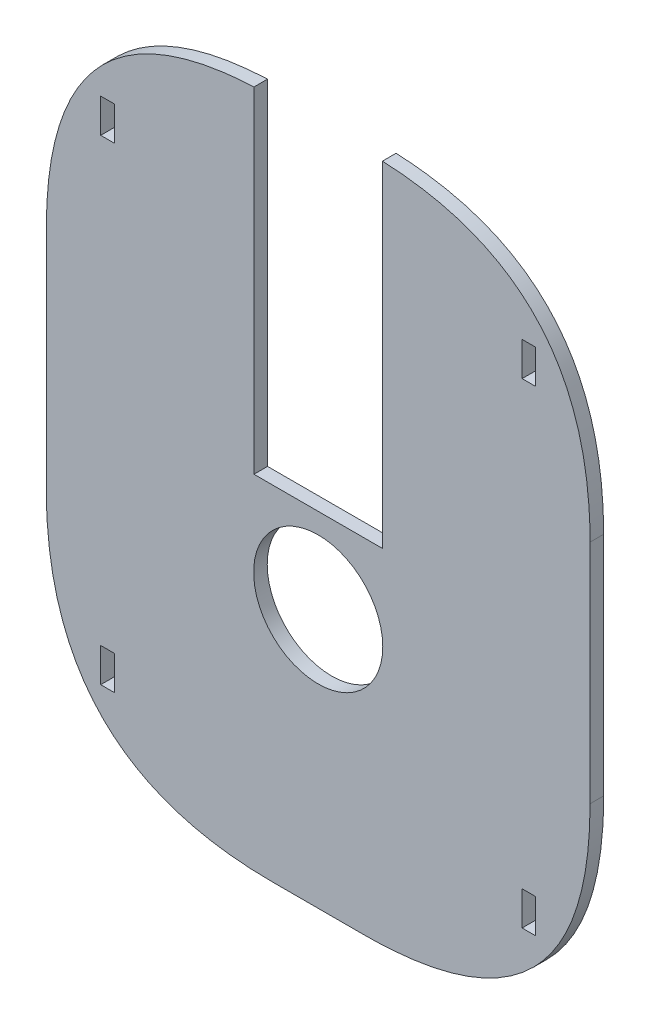
SolidWorks part; units mm, degrees
ref_plane "Front Plane" through (0, 0, 0) normal (0, 0, 1) x (1, 0, 0)
ref_plane "Top Plane" through (0, 0, 0) normal (0, 1, 0) x (1, 0, 0)
ref_plane "Right Plane" through (0, 0, 0) normal (1, 0, 0) x (0, 0, -1)
sketch "Sketch1" plane through (0, 0, 0) normal (0, 0, 1) x (1, 0, 0)
  line L1 (0, 0) -> (203.2, 0)
  line L2 (0, 0) -> (0, 254)
  line L3 (0, 254) -> (203.2, 254)
  line L4 (203.2, 0) -> (203.2, 254)
  dimension "D1" = 254
extrude "Boss-Extrude1" add sketch "Sketch1" along normal blind 5.08
fillet "Fillet1" radius 84.6667 4 edges at (203.2, 254, 2.54) (0, 254, 2.54) (203.2, 0, 2.54) (0, 0, 2.54) conic rho 0.5
sketch "Sketch2" plane through (0, 0, 5.08) normal (0, 0, 1) x (1, 0, 0)
  line L0 (101.6, 254) -> (101.6, 0) construction
  line L1 (118.5333, 254) -> (84.6667, 254) construction
  line L2 (84.6667, 0) -> (118.5333, 0) construction
  line L3 (0, 96.7467) -> (203.2, 96.7467) construction
  line L4 (0, 169.3333) -> (0, 84.6667) construction
  line L5 (203.2, 84.6667) -> (203.2, 169.3333) construction
  circle A0 centre (101.6, 96.7467) radius 24.13
extrude "Cut-Extrude1" cut sketch "Sketch2" against normal through all
sketch "Sketch7" plane through (0, 0, 5.08) normal (0, 0, 1) x (1, 0, 0)
  line L8 (101.6, 215.9) -> (177.8, 215.9) construction
  line L25 (101.6, 38.1) -> (177.8, 38.1) construction
  line L26 (25.4, 215.9) -> (25.4, 222.25)
  line L27 (25.4, 215.9) -> (101.6, 215.9) construction
  line L28 (101.6, 254) -> (101.6, 0) construction
  line L29 (25.4, 222.25) -> (20.32, 222.25)
  line L30 (25.4, 38.1) -> (101.6, 38.1) construction
  line L31 (0, 127) -> (203.2, 127) construction
  line L32 (0, 169.3333) -> (0, 84.6667) construction
  line L33 (203.2, 84.6667) -> (203.2, 169.3333) construction
  line L42 (20.32, 222.25) -> (20.32, 209.55)
  line L43 (20.32, 209.55) -> (25.4, 209.55)
  line L44 (25.4, 209.55) -> (25.4, 215.9)
  line L45 (177.8, 215.9) -> (177.8, 222.25)
  line L46 (177.8, 222.25) -> (182.88, 222.25)
  line L47 (182.88, 222.25) -> (182.88, 209.55)
  line L48 (182.88, 209.55) -> (177.8, 209.55)
  line L49 (177.8, 209.55) -> (177.8, 215.9)
  line L50 (177.8, 38.1) -> (177.8, 44.45)
  line L51 (177.8, 44.45) -> (182.88, 44.45)
  line L52 (182.88, 44.45) -> (182.88, 31.75)
  line L53 (182.88, 31.75) -> (177.8, 31.75)
  line L54 (177.8, 31.75) -> (177.8, 38.1)
  line L55 (25.4, 38.1) -> (25.4, 44.45)
  line L56 (25.4, 44.45) -> (20.32, 44.45)
  line L57 (20.32, 44.45) -> (20.32, 31.75)
  line L58 (20.32, 31.75) -> (25.4, 31.75)
  line L59 (25.4, 31.75) -> (25.4, 38.1)
  dimension "D5" = 88.9
  dimension "D6" = 88.9
  dimension "D3" = 5.08
sketch "Sketch8" plane through (0, 0, 5.08) normal (0, 0, 1) x (1, 0, 0)
  line L0 (-9.9963, 128.4967) -> (213.0772, 128.4967) construction
  line L1 (77.597, 254) -> (125.603, 254)
  line L2 (77.597, 254) -> (77.597, 128.4967)
  line L3 (77.597, 128.4967) -> (125.603, 128.4967)
  line L4 (125.603, 254) -> (125.603, 128.4967)
  line L5 (0, 96.7467) -> (203.2, 96.7467) construction
  line L6 (101.6, 254) -> (101.6, 0) construction
  line L7 (118.5333, 254) -> (84.6667, 254) construction
  point P9 (101.6, 254)
  dimension "D1" = 48.006
  dimension "D2" = 31.75
extrude "Cut-Extrude6" cut sketch "Sketch8" against normal through all
sketch "Sketch9" plane through (0, 0, 0) normal (0, 0, 1) x (1, 0, 0)
  line L1 (60.3112, -121.1497) -> (139.8132, -121.1497) construction
  line L2 (60.3112, -121.1497) -> (60.3112, -43.4257) construction
  line L3 (60.3112, -43.4257) -> (139.8132, -43.4257) construction
  line L4 (139.8132, -121.1497) -> (139.8132, -43.4257) construction
  dimension "D1" = 79.502
  dimension "D2" = 77.724
extrude "Cut-Extrude7" cut sketch "Sketch7" against normal through all
equation "\"FoamCore\" = \".2\""
equation "\"MDF\" = \".2\""
equation "\"GMaterial\"= \".2\""
equation "\"PVCMountDiameter\" = \"0.5in\""
equation "\"PVCMountDistanceToEdge\" = \"0.5\""
equation "\"PVCThickness\" = \"0.13in\""
equation "\"BaseWidth\" = \"8in\""
equation "\"BaseLength\" = \"10in\""
equation "\"BallDiameter\" = \"38mm\""
equation "\"BaseGap\" = \"4in\""
equation "\"FunnelTopDiameter\" = \"8in\""
equation "\"FunnelTopDepth\" = \"0.5in\""
equation "\"BallGap\" = \"0.1in\""
equation "\"FunnelLength\" = 3in"
equation "\"FunnelMaterial\" = 0.1in"
equation "\"FunnelLowerDiameter\" = 1.9in"
equation "\"FunnelDepth\" = 1.5in"
equation "\"AmmoFeederLength\" = 1.5in + 76mm"
equation "\"AmmoFeederCutoffLength\"= \"MovingWheelDiameter\""
equation "\"WheelThickness\" = 0.5in"
equation "\"LauncherWheelDiameter\" = 76mm"
equation "\"MotorFrontLength\" = 0.95in"
equation "\"MotorBodyTotalLength\" = 2.03in"
equation "\"MotorFrontDiameter\" = 1.5in"
equation "\"MotorLowerDriveshaftDiameter\" = 0.46in"
equation "\"MotorLowerDriveshaftThickness\" = 0.25in"
equation "\"MotorFullDriveshaftLength\" = 0.78in"
equation "\"MotorDriveshaftDiameter\" = 0.23in"
equation "\"MotorDriveshaftFlatThickness\" = 0.2in"
equation "\"MotorRearDiameter\" = 31.9mm"
equation "\"MotorDriveshaftBottomToTop\" = 31.1mm"
equation "\"MotorFlatDriveshaftLength\" = 11.7mm"
equation "\"MotorDistanceBetweenLowerandTopHoles\" = 0.5in"
equation "\"MotorMountsDistanceFromEdge\" = 0.06in"
equation "\"MotorScrewMountDiameter\" = 0.1in"
equation "\"MotorScrewMountDepth\" = 0.13in"
equation "\"HBRidgeScrewHoleDeep\" = 0.18in"
equation "\"D1@Sketch1\"=\"BaseLength\""
equation "\"D2@Sketch1\"=\"BaseWidth\""
equation "\"D1@Boss-Extrude1\"=\"MDF\""
equation "\"D1@Fillet1\"=\"BaseLength\" / 3"
equation "\"PVCDiameter\" = 1.5in"
equation "\"FunnelBendLength\" = 2*pi*\"FunnelLowerDiameter\"/2*135"
equation "\"MotorMountWidth\" = \"1.61in\""
equation "\"MotorMountLength\" = \"1.58in\""
equation "\"MotorMountToEdgeGap\" = \"3.3mm\""
equation "\"MotorMountToInsideEdgeGap\" = \"6.5mm\""
equation "\"MotorMountToMountWidthGap\" = \"25.8mm\""
equation "\"MotorMountToMountLengthGap\" = \"20.5mm\""
equation "\"MotorMountMaterialThickness\" = 1.6mm"
equation "\"MotorMountBaseScrewholeDiameter\" = 3.8mm"
equation "\"MotorMountBaseDistancebetweenHoles\" = 0.8in"
equation "\"MotorMountHeight\" = 1.85in"
equation "\"HBridgeWidth\" = 2.25in"
equation "\"HBridgeLength\" = 1.40in"
equation "\"UnoWidth\" = 3.13in"
equation "\"UnoLength\" = 3.06in"
equation "\"BatteryWidth\" = 1.15in"
equation "\"BatteryLength\" = 3.86in"
equation "\"ScrewDiameter\" = 2.7mm"
equation "\"MotorMountFaceScrewtoBase\" = 0.46in"
equation "\"MotorMountFaceDistanceBetweenScrews\" = 0.95in"
equation "\"MotorMountFaceMiddletoEdge\" = 0.16in"
equation "\"MotorMountFaceBottomtoEdge\" = 0.42in"
equation "\"MotorMountCenterholeHeight\" = 1.04in"
equation "\"MotorMountCenterholetoEdge\" = 0.25in"
equation "\"MovingWheelDiameter\" = 76mm"
equation "\"MovingWheelThickness\" = 0.5in"
equation "\"D1@Sketch2\"=\"FunnelLowerDiameter\""
equation "\"BraceLength\" = 1in"
equation "\"BraceVerticalOffset\" = 3.5in"
equation "\"BraceHorizontalOffset\" = 2.5in"
equation "\"D1@Sketch8\"=\"PVCOutsideDiameter\" + \"PVCThickness\""
equation "\"D2@Sketch8\"=\"BaseLength\"/8"
equation "\"BaseToBaseDistance\" = 3in"
equation "\"PVCOutsideDiameter\" = \"PVCDiameter\" + 2*\"PVCThickness\""
equation "\"D1@Sketch9\"=\"UnoWidth\""
equation "\"D2@Sketch9\"=\"UnoLength\""
equation "\"Distancebetweenwalls\" = 6in"
equation "\"D1@Sketch7\"=\"Distancebetweenwalls\"/2"
equation "\"D2@Sketch7\"=\"BraceLength\"/4"
equation "\"D3@Sketch7\"=\"MDF\""
